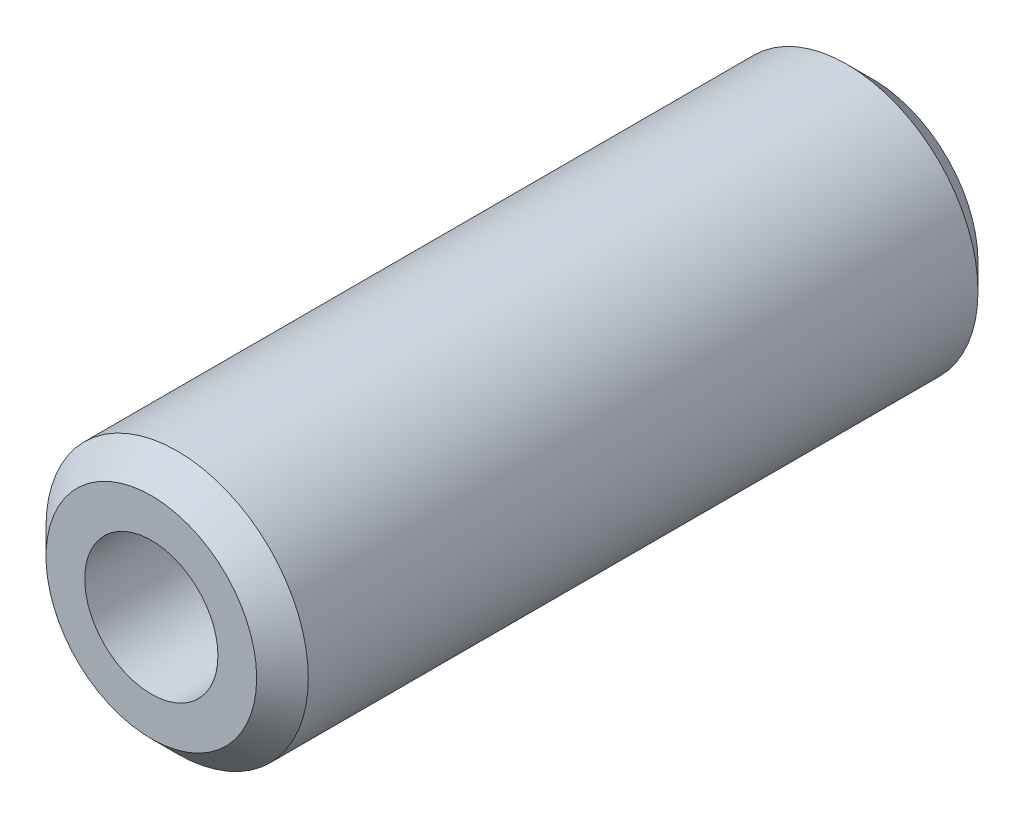
SolidWorks part; units mm, degrees
material "AISI 4340 Steel, normalized"
ref_plane "Front Plane" through (0, 0, 0) normal (0, 0, 1) x (1, 0, 0)
ref_plane "Top Plane" through (0, 0, 0) normal (0, 1, 0) x (1, 0, 0)
ref_plane "Right Plane" through (0, 0, 0) normal (1, 0, 0) x (0, 0, -1)
sketch "Sketch1" plane through (0, 0, 0) normal (0, 0, 1) x (1, 0, 0)
  circle A0 centre (0, 0) radius 12.7
  dimension "D1" = 25.4
extrude "Boss-Extrude1" add sketch "Sketch1" along normal blind 69.85
sketch "Sketch2" plane through (0, 0, 69.85) normal (0, 0, 1) x (1, 0, 0)
  circle A0 centre (0, 0) radius 6.45
  dimension "D1" = 12.9
extrude "Cut-Extrude1" cut sketch "Sketch2" against normal through all both and the other way through all
chamfer "Chamfer1" distance 2.5 angle 45 2 edges at (12.7, 0, 69.85) (12.7, 0, 0)
